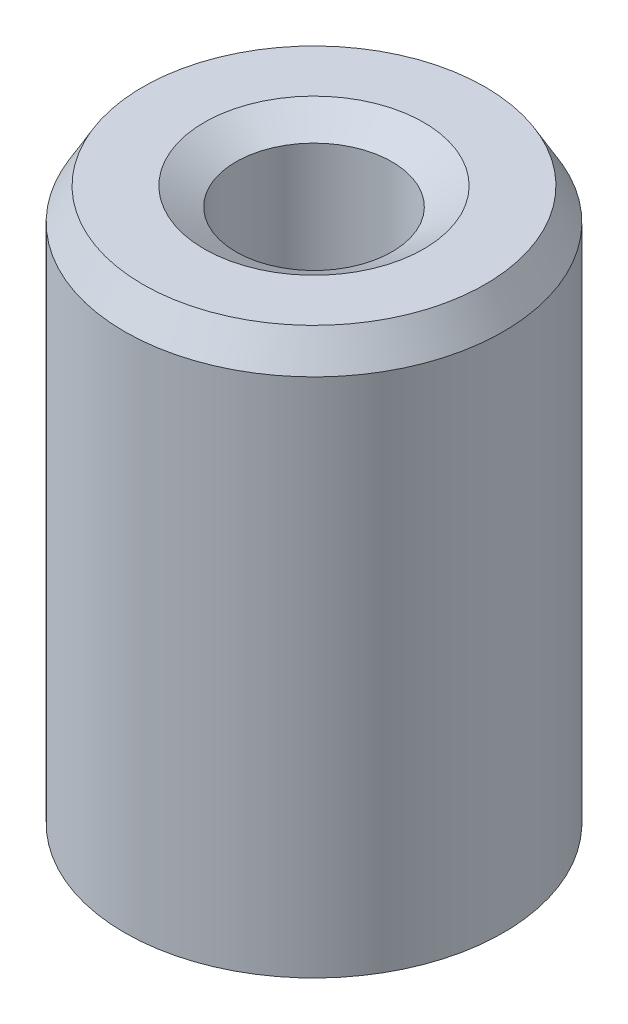
SolidWorks part; units mm, degrees
ref_plane "Front Plane" through (0, 0, 0) normal (0, 0, 1) x (1, 0, 0)
ref_plane "Top Plane" through (0, 0, 0) normal (0, 1, 0) x (1, 0, 0)
ref_plane "Right Plane" through (0, 0, 0) normal (1, 0, 0) x (0, 0, -1)
sketch "Sketch1" plane through (0, 0, 0) normal (0, 1, 0) x (1, 0, 0)
  circle A0 centre (0, 0) radius 20
  dimension "SLEEVE_OD" = 40
extrude "Boss-Extrude1" add sketch "Sketch1" along normal blind 60.246
sketch "Sketch2" plane through (0, 0, 0) normal (0, 1, 0) x (1, 0, 0)
  circle A0 centre (0, 0) radius 8.2398
  dimension "BORE_D" = 16.4797
extrude "Cut-Extrude1" cut sketch "Sketch2" along normal through all
chamfer "Chamfer1" distance 3.3467 angle 30 4 edges at (0, 60.246, 8.2398) (0, 0, 8.2398) (0, 0, 20) (0, 60.246, 20) first distance on face at (0, 60.246, 8.2398) first distance on face at (0, 0, 8.2398) first distance on face at (0, 60.246, 20)
